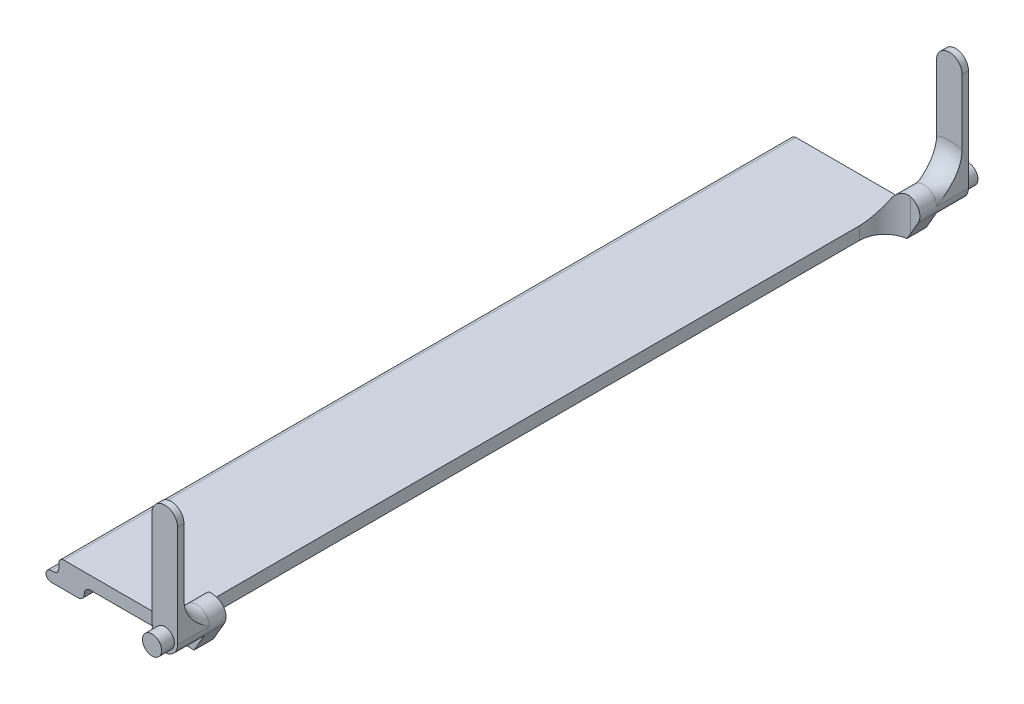
SolidWorks part; units mm, degrees
material "ABS"
ref_plane "Front Plane" through (0, 0, 0) normal (0, 0, 1) x (1, 0, 0)
ref_plane "Top Plane" through (0, 0, 0) normal (0, 1, 0) x (1, 0, 0)
ref_plane "Right Plane" through (0, 0, 0) normal (1, 0, 0) x (0, 0, -1)
sketch "Sketch1" plane through (0, 0, 0) normal (0, 0, 1) x (1, 0, 0)
  line B0 (-33.7058, -6.35) -> (-33.7058, -3.175)
  line B1 (-33.7058, -6.35) -> (0, -6.35)
  line B2 (0, -6.35) -> (2.7496, -1.5875)
  line B3 (-33.7058, -3.175) -> (-5.4993, -3.175)
  line B4 (-2.7496, 1.5875) -> (-5.4993, -3.175)
  circle B5 centre (0, 0) radius 2.3812
  circle B6 centre (0, 0) radius 3.175
sketch_block_instance "trap_door_geometry-1"
sketch_block "trap_door_geometry" parameters "D1"=4.7625, "D2"=6.35
extrude "Boss-Extrude1" add sketch "Sketch1" along normal mid plane 182.2196 contours B6 B4 B3 B0 B1 B2 | B6 B5 | B5 region at (-15.5478, -4.5785, 0) region at (-1.5426, -2.6719, 0) region at (0, 0, 0)
sketch "Sketch2" plane through (0, 0, 0) normal (0, 1, 0) x (1, 0, 0)
  line L0 (-5.4993, -91.1098) -> (-5.4993, 91.1098) construction
  line L1 (3.175, -91.1098) -> (3.175, 91.1098) construction
  line L2 (-5.4993, -91.1098) -> (-5.4993, 91.1098)
  line L3 (3.175, -91.1098) -> (3.175, 91.1098)
  line L4 (3.175, -86.3473) -> (-5.4993, -86.3473)
  line L5 (-2.7496, -91.1098) -> (3.175, -91.1098) construction
  line L6 (0, 0) -> (50000, 0) construction
  line L7 (3.175, 86.3473) -> (-5.4993, 86.3473)
  dimension "D1" = 4.7625
extrude "Cut-Extrude1" cut sketch "Sketch2" against normal through all both and the other way through all contours L2 L6 L3 L7 | L6 L2 L4 L3 region at (-1.1621, 0, 0)
sketch "Sketch3" plane through (0, 0, 91.1098) normal (0, 0, 1) x (1, 0, 0)
  circle A0 centre (0, 0) radius 3.175
  dimension "D1" = 6.35
extrude "Boss-Extrude2" add sketch "Sketch3" along normal blind 7.3152
sketch "Sketch4" plane through (0, 0, 98.425) normal (0, 0, 1) x (1, 0, 0)
  circle A0 centre (0, 0) radius 2.3813
  dimension "D1" = 4.7625
extrude "Boss-Extrude3" add sketch "Sketch4" along normal blind 3.175
mirror "Mirror1" about plane through (0, 0, 0) normal (0, 0, 1) of "Boss-Extrude2", "Boss-Extrude3"
sketch "Sketch6" plane through (0, 0, -98.425) normal (0, 0, -1) x (-1, 0, 0)
  line L0 (0, 0) -> (0, 50000) construction
  line L1 (2.7496, 1.5875) -> (5.4993, -3.175) construction
  line L2 (2.7496, 1.5875) -> (3.175, 0.8507)
  line L3 (-3.175, 25.4) -> (-3.175, 0)
  line L4 (3.175, 25.4) -> (3.175, 0.8507)
  circle A0 centre (0, 0) radius 3.175 construction
  arc A1 (2.7496, 1.5875) -> (-3.175, 0) centre (0, 0) ccw
  arc A2 (3.175, 25.4) -> (-3.175, 25.4) centre (0, 25.4) ccw
  dimension "D1" = 6.35
  dimension "D2" = 25.4
extrude "Boss-Extrude4" add sketch "Sketch6" against normal blind 1.5875
mirror "Mirror2" about plane through (0, 0, 0) normal (0, 0, 1) of "Boss-Extrude4"
fillet "Fillet2" radius 6.35 2 edges at (-5.4993, -4.7625, 86.3473) (-5.4993, -4.7625, -86.3473)
fillet "Fillet4" radius 6.35 2 edges at (0.8218, 3.0668, 96.8375) (0.8218, 3.0668, -96.8375)
sketch "Sketch7" plane through (0, -6.35, 0) normal (0, -1, 0) x (1, 0, 0)
  line L0 (-27.3558, 91.1098) -> (-27.3558, -91.1098)
  line L6 (0, -91.1098) -> (0, -86.2901)
  line L7 (-5.4993, -79.9973) -> (-5.4993, 79.9973)
  line L8 (0, 86.2901) -> (0, 91.1098)
  line L9 (0, 91.1098) -> (-33.7058, 91.1098)
  line L10 (-33.7058, 91.1098) -> (-33.7058, -91.1098)
  line L11 (-33.7058, -91.1098) -> (0, -91.1098)
  line L15 (-27.3558, 91.1098) -> (-33.7058, 91.1098)
  line L16 (-33.7058, 91.1098) -> (-33.7058, -91.1098)
  line L17 (-33.7058, -91.1098) -> (-27.3558, -91.1098)
  arc A2 (-5.4993, -79.9973) -> (0, -86.2901) centre (0.8507, -79.9973) ccw
  arc A3 (0, 86.2901) -> (-5.4993, 79.9973) centre (0.8507, 79.9973) ccw
  dimension "D2" = 6.35
  dimension "D1" = 0
extrude "Boss-Extrude5" add sketch "Sketch7" along normal blind 3.175
sketch "Sketch10" plane through (-33.7058, 0, 0) normal (-1, 0, 0) x (0, 0, 1)
  line L0 (91.1098, -6.985) -> (-91.1098, -6.985)
  line L4 (-91.1098, -3.175) -> (-91.1098, -9.525)
  line L5 (-91.1098, -9.525) -> (91.1098, -9.525)
  line L6 (91.1098, -9.525) -> (91.1098, -3.175)
  line L7 (91.1098, -3.175) -> (-91.1098, -3.175)
  line L8 (-91.1098, -3.175) -> (-91.1098, -9.525)
  line L9 (-91.1098, -9.525) -> (91.1098, -9.525)
  line L10 (91.1098, -9.525) -> (91.1098, -3.175)
  line L11 (91.1098, -3.175) -> (-91.1098, -3.175)
  line M6 (-91.1098, -3.175) -> (-91.1098, -9.525)
  line M7 (-91.1098, -9.525) -> (91.1098, -9.525)
  line M8 (91.1098, -9.525) -> (91.1098, -3.175)
  dimension "D2" = 2.54
  dimension "D1" = 0
extrude "Boss-Extrude6" add sketch "Sketch10" along normal blind 3.175 contours L0 M8 M6 M7 region at (-33.7058, -8.255, 0)
fillet "Fillet5" radius 1.27 4 edges at (-36.8808, -9.525, 0) (-36.8808, -6.985, 0) (-33.7058, -6.985, 0) (-33.7058, -3.175, 0)
fillet "Fillet6" radius 1.524 2 edges at (-27.3558, -6.35, 0) (-27.3558, -9.525, 0)
